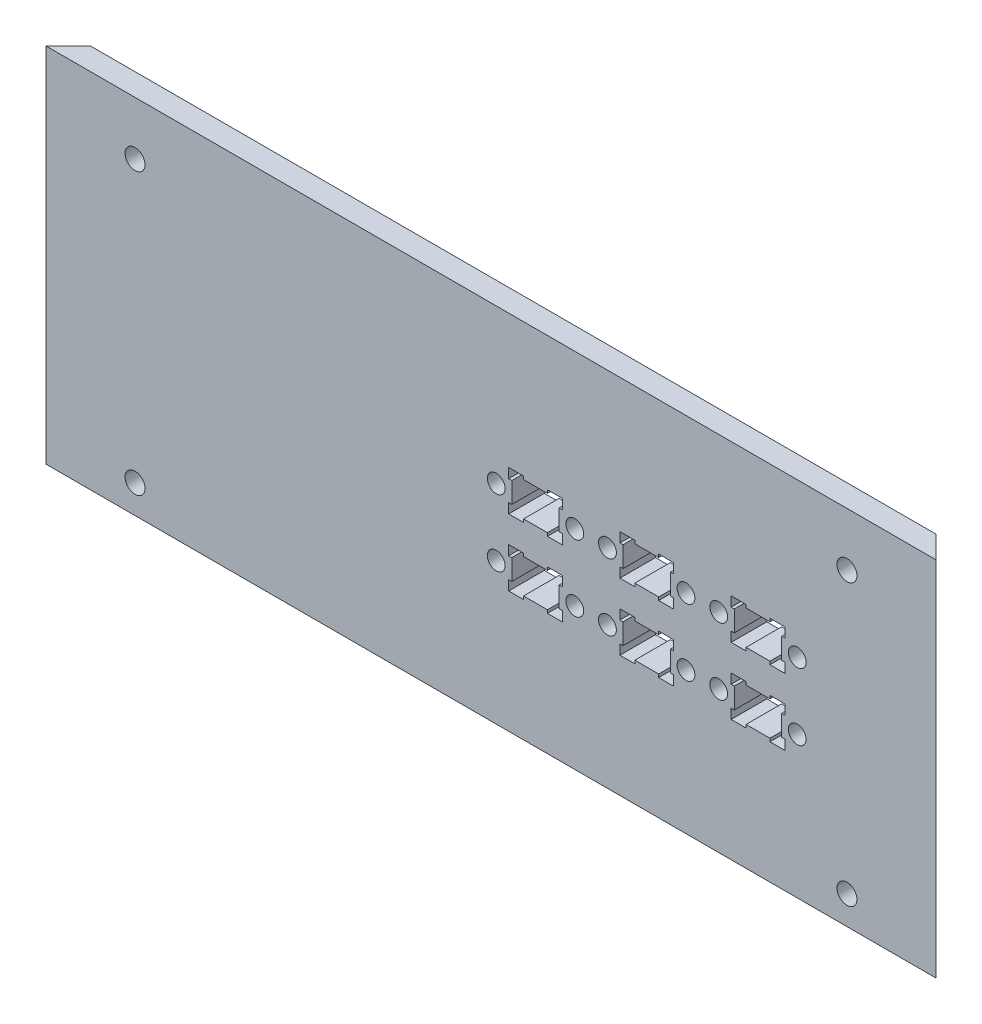
SolidWorks part; units mm, degrees
ref_plane "Front Plane" through (0, 0, 0) normal (0, 0, 1) x (1, 0, 0)
ref_plane "Top Plane" through (0, 0, 0) normal (0, 1, 0) x (1, 0, 0)
ref_plane "Right Plane" through (0, 0, 0) normal (1, 0, 0) x (0, 0, -1)
sketch "Sketch1" plane through (0, 0, 0) normal (0, 0, 1) x (1, 0, 0)
  line L0 (100, 84) -> (100, -37.3998) construction
  line L1 (0, 0) -> (200, 0)
  line L2 (0, 0) -> (0, 84)
  line L3 (0, 84) -> (200, 84)
  line L4 (200, 0) -> (200, 84)
  line L5 (0, 42) -> (200, 42) construction
  circle A0 centre (20, 9) radius 2.25
  circle A1 centre (180, 9) radius 2.25
  circle A4 centre (20, 72) radius 2.25
  circle A5 centre (180, 72) radius 2.25
  dimension "D3" = 20
  dimension "D5" = 4.5
  dimension "D1" = 84
  dimension "D2" = 200
  dimension "D4" = 9
  dimension "D6" = 2
  dimension "D7" = 12
extrude "Boss-Extrude1" add sketch "Sketch1" against normal blind 5
sketch "Sketch2" plane through (0, 0, -5) normal (0, 0, -1) x (-1, 0, 0)
  line L0 (0, 0) -> (-200, 0) construction
  line L1 (0, 0) -> (-200, 0) construction
  line L2 (0, 5) -> (-200, 5)
  line L3 (-200, 5) -> (-200, 84)
  line L4 (-200, 84) -> (0, 84)
  line L5 (0, 84) -> (0, 5)
  circle A1 centre (-20, 9) radius 2.25 construction
  circle A2 centre (-180, 9) radius 2.25 construction
  circle A5 centre (-20, 9) radius 2.25
  circle A6 centre (-180, 9) radius 2.25
  circle A8 centre (-20, 72) radius 2.25 construction
  circle A9 centre (-180, 72) radius 2.25 construction
  circle A10 centre (-20, 72) radius 2.25
  circle A11 centre (-180, 72) radius 2.25
  dimension "D1" = 5
extrude "Boss-Extrude2" add sketch "Sketch2" along normal blind 3
chamfer "Chamfer1" distance 8 angle 45 3 edges at (200, 44.5, -8) (0, 44.5, -8) (100, 84, -8)
chamfer "Chamfer3" distance 3 angle 45 1 edges at (100, 84, -8)
sketch "Sketch3" plane through (100, 0, -100) normal (0.7071, 0, -0.7071) x (-0.7071, 0, -0.7071)
  line L0 (-141.4214, 0) -> (-141.4214, 2.6)
  line L1 (-141.4214, 0) -> (-141.4214, 84) construction
  line L2 (-141.4214, 2.6) -> (-134.3503, 2.6)
  line L4 (-134.3503, 2.6) -> (-134.3503, 0)
  line L5 (-134.3503, 0) -> (-141.4214, 0)
  line L6 (-130.1076, 5) -> (-134.3503, 5) construction
  dimension "D1" = 2.4
extrude "Cut-Extrude1" cut sketch "Sketch3" along direction (1, 0, 0) on the side against the normal through all
sketch "Sketch4" plane through (0, 0, 0) normal (0, 0, 1) x (1, 0, 0)
  line L0 (160, 37.8653) -> (160, 31.0153) construction
  line L5 (155.075, 31.0153) -> (164.925, 37.8653) construction
  line L6 (155.075, 37.8653) -> (164.925, 31.0153) construction
  line L7 (163.085, 38.5653) -> (165.625, 38.5653) construction
  line L8 (163.085, 38.5653) -> (163.085, 37.8653) construction
  line L10 (165.625, 38.5653) -> (165.625, 37.1653) construction
  line L11 (163.085, 38.5653) -> (165.625, 37.1653) construction
  line L12 (163.085, 37.1653) -> (165.625, 38.5653) construction
  line L14 (165.625, 37.1653) -> (165.625, 37.8653)
  line L15 (165.625, 37.8653) -> (164.925, 37.8653) construction
  line L16 (164.925, 37.1653) -> (164.925, 37.8653) construction
  line L17 (155.075, 34.4403) -> (164.925, 34.4403) construction
  line L18 (154.375, 38.5653) -> (154.375, 37.1653) construction
  line L19 (156.915, 38.5653) -> (154.375, 38.5653) construction
  line L20 (156.915, 38.5653) -> (156.915, 37.8653) construction
  line L22 (165.625, 30.3153) -> (165.625, 31.7153) construction
  line L23 (163.085, 30.3153) -> (165.625, 30.3153) construction
  line L24 (163.085, 30.3153) -> (163.085, 31.0153) construction
  line L27 (156.915, 30.3153) -> (156.915, 31.0153) construction
  line L28 (156.915, 30.3153) -> (154.375, 30.3153) construction
  line L29 (154.375, 30.3153) -> (154.375, 31.7153) construction
  line L30 (160, 84) -> (160, 2.6) construction
  line L31 (200, 84) -> (0, 84) construction
  line L32 (0, 2.6) -> (200, 2.6) construction
  line L33 (200, 34.4403) -> (0, 34.4403) construction
  line L34 (200, 2.6) -> (200, 84) construction
  line L35 (0, 84) -> (0, 2.6) construction
  line L40 (155.075, 37.1653) -> (154.375, 37.1653) construction
  line L41 (155.075, 31.7153) -> (154.375, 31.7153) construction
  line L42 (165.625, 31.7153) -> (164.925, 31.7153) construction
  line L43 (164.925, 37.1653) -> (165.625, 37.1653) construction
  line L44 (165.325, 36.7653) -> (166.025, 36.7653)
  line L45 (164.925, 37.1653) -> (164.925, 31.7153) construction
  line L46 (163.085, 31.0153) -> (156.915, 31.0153) construction
  line L47 (155.075, 31.7153) -> (155.075, 37.1653) construction
  line L48 (156.915, 37.8653) -> (163.085, 37.8653) construction
  line L49 (165.325, 36.7653) -> (165.325, 32.1153)
  line L50 (166.025, 32.1153) -> (165.325, 32.1153)
  line L51 (166.025, 29.9153) -> (166.025, 32.1153)
  line L52 (162.685, 29.9153) -> (166.025, 29.9153)
  line L53 (162.685, 29.9153) -> (162.685, 30.6153)
  line L54 (162.685, 30.6153) -> (157.315, 30.6153)
  line L55 (157.315, 29.9153) -> (157.315, 30.6153)
  line L56 (157.315, 29.9153) -> (153.975, 29.9153)
  line L57 (153.975, 29.9153) -> (153.975, 32.1153)
  line L58 (154.675, 32.1153) -> (153.975, 32.1153)
  line L59 (154.675, 32.1153) -> (154.675, 36.7653)
  line L60 (154.675, 36.7653) -> (153.975, 36.7653)
  line L61 (153.975, 38.9653) -> (153.975, 36.7653)
  line L62 (157.315, 38.9653) -> (153.975, 38.9653)
  line L63 (157.315, 38.9653) -> (157.315, 38.2653)
  line L64 (157.315, 38.2653) -> (162.685, 38.2653)
  line L65 (162.685, 38.9653) -> (162.685, 38.2653)
  line L66 (162.685, 38.9653) -> (166.025, 38.9653)
  line L67 (166.025, 38.9653) -> (166.025, 36.7653)
  line L164 (160, 34.4403) -> (151.175, 34.4403) construction
  line L165 (140.325, 36.7653) -> (141.025, 36.7653)
  line L166 (141.025, 38.9653) -> (141.025, 36.7653)
  line L167 (137.685, 38.9653) -> (141.025, 38.9653)
  line L168 (137.685, 38.9653) -> (137.685, 38.2653)
  line L169 (132.315, 38.2653) -> (137.685, 38.2653)
  line L170 (132.315, 38.9653) -> (132.315, 38.2653)
  line L171 (132.315, 38.9653) -> (128.975, 38.9653)
  line L172 (128.975, 38.9653) -> (128.975, 36.7653)
  line L173 (129.675, 36.7653) -> (128.975, 36.7653)
  line L174 (129.675, 32.1153) -> (129.675, 36.7653)
  line L175 (129.675, 32.1153) -> (128.975, 32.1153)
  line L176 (128.975, 29.9153) -> (128.975, 32.1153)
  line L177 (132.315, 29.9153) -> (128.975, 29.9153)
  line L178 (132.315, 29.9153) -> (132.315, 30.6153)
  line L179 (137.685, 30.6153) -> (132.315, 30.6153)
  line L180 (137.685, 29.9153) -> (137.685, 30.6153)
  line L181 (137.685, 29.9153) -> (141.025, 29.9153)
  line L182 (141.025, 29.9153) -> (141.025, 32.1153)
  line L183 (141.025, 32.1153) -> (140.325, 32.1153)
  line L184 (140.325, 36.7653) -> (140.325, 32.1153)
  line L185 (115.325, 36.7653) -> (116.025, 36.7653)
  line L186 (116.025, 38.9653) -> (116.025, 36.7653)
  line L187 (112.685, 38.9653) -> (116.025, 38.9653)
  line L188 (112.685, 38.9653) -> (112.685, 38.2653)
  line L189 (107.315, 38.2653) -> (112.685, 38.2653)
  line L190 (107.315, 38.9653) -> (107.315, 38.2653)
  line L191 (107.315, 38.9653) -> (103.975, 38.9653)
  line L192 (103.975, 38.9653) -> (103.975, 36.7653)
  line L193 (104.675, 36.7653) -> (103.975, 36.7653)
  line L194 (104.675, 32.1153) -> (104.675, 36.7653)
  line L195 (104.675, 32.1153) -> (103.975, 32.1153)
  line L196 (103.975, 29.9153) -> (103.975, 32.1153)
  line L197 (107.315, 29.9153) -> (103.975, 29.9153)
  line L198 (107.315, 29.9153) -> (107.315, 30.6153)
  line L199 (112.685, 30.6153) -> (107.315, 30.6153)
  line L200 (112.685, 29.9153) -> (112.685, 30.6153)
  line L201 (112.685, 29.9153) -> (116.025, 29.9153)
  line L202 (116.025, 29.9153) -> (116.025, 32.1153)
  line L203 (116.025, 32.1153) -> (115.325, 32.1153)
  line L204 (115.325, 36.7653) -> (115.325, 32.1153)
  line L205 (140.325, 51.7653) -> (141.025, 51.7653)
  line L206 (141.025, 53.9653) -> (141.025, 51.7653)
  line L207 (137.685, 53.9653) -> (141.025, 53.9653)
  line L208 (137.685, 53.9653) -> (137.685, 53.2653)
  line L209 (132.315, 53.2653) -> (137.685, 53.2653)
  line L210 (132.315, 53.9653) -> (132.315, 53.2653)
  line L211 (132.315, 53.9653) -> (128.975, 53.9653)
  line L212 (128.975, 53.9653) -> (128.975, 51.7653)
  line L213 (129.675, 51.7653) -> (128.975, 51.7653)
  line L214 (129.675, 47.1153) -> (129.675, 51.7653)
  line L215 (129.675, 47.1153) -> (128.975, 47.1153)
  line L216 (128.975, 44.9153) -> (128.975, 47.1153)
  line L217 (132.315, 44.9153) -> (128.975, 44.9153)
  line L218 (132.315, 44.9153) -> (132.315, 45.6153)
  line L219 (137.685, 45.6153) -> (132.315, 45.6153)
  line L220 (137.685, 44.9153) -> (137.685, 45.6153)
  line L221 (137.685, 44.9153) -> (141.025, 44.9153)
  line L222 (141.025, 44.9153) -> (141.025, 47.1153)
  line L223 (141.025, 47.1153) -> (140.325, 47.1153)
  line L224 (140.325, 51.7653) -> (140.325, 47.1153)
  line L225 (115.325, 51.7653) -> (116.025, 51.7653)
  line L226 (116.025, 53.9653) -> (116.025, 51.7653)
  line L227 (112.685, 53.9653) -> (116.025, 53.9653)
  line L228 (112.685, 53.9653) -> (112.685, 53.2653)
  line L229 (107.315, 53.2653) -> (112.685, 53.2653)
  line L230 (107.315, 53.9653) -> (107.315, 53.2653)
  line L231 (107.315, 53.9653) -> (103.975, 53.9653)
  line L232 (103.975, 53.9653) -> (103.975, 51.7653)
  line L233 (104.675, 51.7653) -> (103.975, 51.7653)
  line L234 (104.675, 47.1153) -> (104.675, 51.7653)
  line L235 (104.675, 47.1153) -> (103.975, 47.1153)
  line L236 (103.975, 44.9153) -> (103.975, 47.1153)
  line L237 (107.315, 44.9153) -> (103.975, 44.9153)
  line L238 (107.315, 44.9153) -> (107.315, 45.6153)
  line L239 (112.685, 45.6153) -> (107.315, 45.6153)
  line L240 (112.685, 44.9153) -> (112.685, 45.6153)
  line L241 (112.685, 44.9153) -> (116.025, 44.9153)
  line L242 (116.025, 44.9153) -> (116.025, 47.1153)
  line L243 (116.025, 47.1153) -> (115.325, 47.1153)
  line L244 (115.325, 51.7653) -> (115.325, 47.1153)
  line L245 (165.325, 51.7653) -> (166.025, 51.7653)
  line L246 (166.025, 53.9653) -> (166.025, 51.7653)
  line L247 (162.685, 53.9653) -> (166.025, 53.9653)
  line L248 (162.685, 53.9653) -> (162.685, 53.2653)
  line L249 (157.315, 53.2653) -> (162.685, 53.2653)
  line L250 (157.315, 53.9653) -> (157.315, 53.2653)
  line L251 (157.315, 53.9653) -> (153.975, 53.9653)
  line L252 (153.975, 53.9653) -> (153.975, 51.7653)
  line L253 (154.675, 51.7653) -> (153.975, 51.7653)
  line L254 (154.675, 47.1153) -> (154.675, 51.7653)
  line L255 (154.675, 47.1153) -> (153.975, 47.1153)
  line L256 (153.975, 44.9153) -> (153.975, 47.1153)
  line L257 (157.315, 44.9153) -> (153.975, 44.9153)
  line L258 (157.315, 44.9153) -> (157.315, 45.6153)
  line L259 (162.685, 45.6153) -> (157.315, 45.6153)
  line L260 (162.685, 44.9153) -> (162.685, 45.6153)
  line L261 (162.685, 44.9153) -> (166.025, 44.9153)
  line L262 (166.025, 44.9153) -> (166.025, 47.1153)
  line L263 (166.025, 47.1153) -> (165.325, 47.1153)
  line L264 (165.325, 51.7653) -> (165.325, 47.1153)
  circle A0 centre (151.175, 34.4403) radius 2
  circle A1 centre (168.825, 34.4403) radius 2
  circle A2 centre (126.175, 34.4403) radius 2
  circle A3 centre (143.825, 34.4403) radius 2
  circle A4 centre (101.175, 34.4403) radius 2
  circle A5 centre (118.825, 34.4403) radius 2
  circle A6 centre (126.175, 49.4403) radius 2
  circle A7 centre (143.825, 49.4403) radius 2
  circle A8 centre (101.175, 49.4403) radius 2
  circle A9 centre (118.825, 49.4403) radius 2
  circle A10 centre (151.175, 49.4403) radius 2
  circle A11 centre (168.825, 49.4403) radius 2
  point P0 (160, 34.4403)
  point P5 (164.355, 37.8653)
  point P29 (0, 0)
  point P43 (0, 0)
  point P53 (160, 34.4403)
  dimension "D2" = 5.625
  dimension "D3" = 3.085
  dimension "D4" = 0.57
  dimension "D5" = 2.725
  dimension "D6" = 40
  dimension "D9" = 0.4
  dimension "D7" = 3
  dimension "D10" = 2
other "AlignGroup1" parameters "D11"=4, "D1"=0, "D2"=5.625, "D3"=3.085, "D4"=1.27, "D5"=0.57, "D6"=5.625, "D7"=3.085, "D8"=1.84, "D9"=3.425, "D10"=4.125
extrude "Cut-Extrude3" cut sketch "Sketch4" against normal through all
